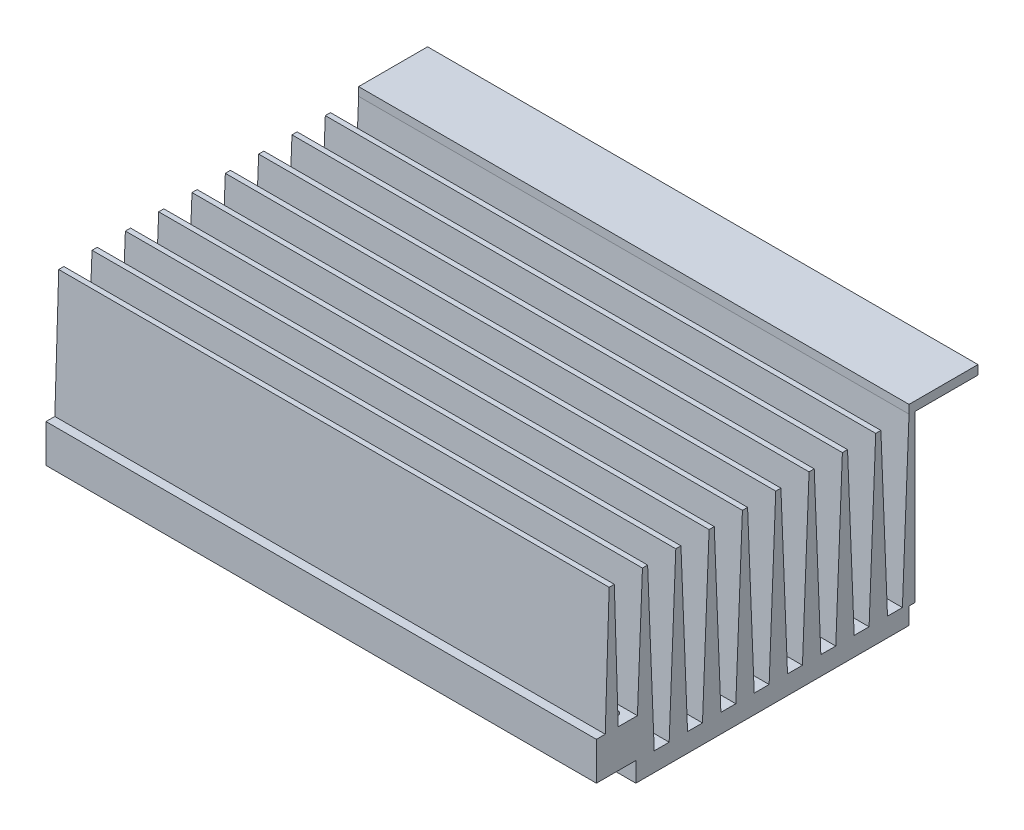
SolidWorks part; units mm, degrees
ref_plane "Front Plane" through (0, 0, 0) normal (0, 0, 1) x (1, 0, 0)
ref_plane "Top Plane" through (0, 0, 0) normal (0, 1, 0) x (1, 0, 0)
ref_plane "Right Plane" through (0, 0, 0) normal (1, 0, 0) x (0, 0, -1)
sketch "Sketch1" plane through (0, 0, 0) normal (0, 1, 0) x (1, 0, 0)
  line L1 (0, 0) -> (195.4375, 0)
  line L2 (0, 0) -> (0, 97)
  line L3 (0, 97) -> (195.4375, 97)
  line L4 (195.4375, 0) -> (195.4375, 97)
  dimension "D1" = 97
  dimension "D2" = 195.4375
extrude "Boss-Extrude1" add sketch "Sketch1" along normal blind 65
sketch "Sketch2" plane through (0, 0, 0) normal (-1, 0, 0) x (0, 0, 1)
  line L0 (-97, 65) -> (-94.65, 6.7)
  line L2 (-94.65, 6.7) -> (-89.35, 6.7)
  line L3 (-89.35, 6.7) -> (-87, 65)
  line L4 (-97, 65) -> (0, 65) construction
  line L5 (-87, 65) -> (-97, 65)
  line L7 (-97, 0) -> (0, 0) construction
  line L8 (-92, 6.7) -> (-92, 65) construction
  line L37 (-75.1687, 65) -> (-85.1687, 65)
  line L38 (-85.1687, 65) -> (-82.8187, 6.7)
  line L39 (-82.8187, 6.7) -> (-77.5187, 6.7)
  line L40 (-77.5187, 6.7) -> (-75.1687, 65)
  line L41 (-63.3375, 65) -> (-73.3375, 65)
  line L42 (-73.3375, 65) -> (-70.9875, 6.7)
  line L43 (-70.9875, 6.7) -> (-65.6875, 6.7)
  line L44 (-65.6875, 6.7) -> (-63.3375, 65)
  line L45 (-51.5062, 65) -> (-61.5062, 65)
  line L46 (-61.5062, 65) -> (-59.1562, 6.7)
  line L47 (-59.1562, 6.7) -> (-53.8563, 6.7)
  line L48 (-53.8563, 6.7) -> (-51.5062, 65)
  line L49 (-39.675, 65) -> (-49.675, 65)
  line L50 (-49.675, 65) -> (-47.325, 6.7)
  line L51 (-47.325, 6.7) -> (-42.025, 6.7)
  line L52 (-42.025, 6.7) -> (-39.675, 65)
  line L53 (-27.8437, 65) -> (-37.8437, 65)
  line L54 (-37.8437, 65) -> (-35.4937, 6.7)
  line L55 (-35.4937, 6.7) -> (-30.1937, 6.7)
  line L56 (-30.1937, 6.7) -> (-27.8437, 65)
  line L57 (-16.0125, 65) -> (-26.0125, 65)
  line L58 (-26.0125, 65) -> (-23.6625, 6.7)
  line L59 (-23.6625, 6.7) -> (-18.3625, 6.7)
  line L60 (-18.3625, 6.7) -> (-16.0125, 65)
  line L61 (-4.1812, 65) -> (-14.1812, 65)
  line L62 (-14.1812, 65) -> (-11.8313, 6.7)
  line L63 (-11.8313, 6.7) -> (-6.5313, 6.7)
  line L64 (-6.5313, 6.7) -> (-4.1812, 65)
  line L65 (7.65, 65) -> (-2.35, 65)
  line L66 (-2.35, 65) -> (0, 6.7)
  line L67 (0, 6.7) -> (5.3, 6.7)
  line L68 (5.3, 6.7) -> (7.65, 65)
  line L69 (0, 65) -> (0, 0) construction
  point P13 (-7.482, 65)
  point P45 (-1.8807, 65)
  point P46 (0, 6.7)
  dimension "D1" = 10
  dimension "D2" = 5.3
  dimension "D3" = 6.7
  dimension "D4" = 9
extrude "Cut-Extrude1" cut sketch "Sketch2" against normal through all
ref_plane "Plane1" through (0, 7, 0) normal (0, -1, 0) x (-1, 0, 0)
sketch "Sketch4" plane through (0, 7, 0) normal (0, -1, 0) x (-1, 0, 0)
  line L0 (-195.4375, 0) -> (-195.4375, 97) construction
  line L1 (0, 1) -> (-195.4375, 1)
  line L2 (0, 1) -> (0, -14)
  line L3 (0, -14) -> (-195.4375, -14)
  line L4 (-195.4375, 1) -> (-195.4375, -14)
  line L5 (0, 97) -> (0, 0) construction
  point P5 (-148.1218, -9.5046)
  point P6 (-147.4038, 1.3296)
  point P7 (-148.5308, 0.9317)
  point P8 (-149.4906, 0.7439)
  point P12 (0, 1)
  point P15 (0, -7.7852)
  dimension "D1" = 1
  dimension "D2" = 15
extrude "Boss-Extrude2" add sketch "Sketch4" against normal blind 13.5
sketch "Sketch5" plane through (0, 0, 0) normal (-1, 0, 0) x (0, 0, 1)
  line L0 (6.2656, 20.5) -> (7.65, 65)
  line L1 (14, 20.5) -> (-0.5563, 20.5) construction
  line L2 (7.65, 65) -> (9.4813, 65)
  line L3 (9.4813, 65) -> (10.8656, 20.5)
  line L4 (-14.1812, 65) -> (-4.1812, 65) construction
  line L5 (-2.35, 65) -> (7.65, 65) construction
  line L6 (-4.1812, 65) -> (-2.35, 65) construction
  line L7 (6.2656, 20.5) -> (10.8656, 20.5)
  line L8 (8.5656, 65) -> (8.5656, 20.5) construction
  line L10 (-21.0125, 6.7) -> (-9.1813, 6.7) construction
  line L11 (-23.6625, 6.7) -> (-18.3625, 6.7) construction
  line L12 (-11.8313, 6.7) -> (-6.5313, 6.7) construction
  dimension "D1" = 4.6
extrude "Boss-Extrude3" add sketch "Sketch5" against normal up to surface (195.4375 mm away) up to face at (195.4375, 31.8475, -42.2705)
ref_plane "Plane2" through (0, 6, 0) normal (0, -1, 0) x (-1, 0, 0)
sketch "Sketch6" plane through (0, 6, 0) normal (0, -1, 0) x (-1, 0, 0)
  line L0 (-195.4375, 0) -> (-195.4375, 97) construction
  line L1 (0, 97) -> (-195.4375, 97)
  line L2 (0, 97) -> (0, 99.19)
  line L3 (0, 99.19) -> (-195.4375, 99.19)
  line L4 (-195.4375, 97) -> (-195.4375, 99.19)
  line L5 (0, 97) -> (0, 0) construction
  line L6 (-195.4375, 97) -> (0, 97) construction
  dimension "D1" = 2.19
extrude "Boss-Extrude4" add sketch "Sketch6" against normal blind 62
sketch "Sketch7" plane through (0, 0, -99.19) normal (0, 0, -1) x (-1, 0, 0)
  line L0 (0, 68) -> (0, 6) construction
  line L1 (-195.4375, 68) -> (0, 68)
  line L2 (-195.4375, 68) -> (-195.4375, 64.76)
  line L3 (-195.4375, 64.76) -> (0, 64.76)
  line L4 (0, 68) -> (0, 64.76)
  point P7 (0, 63.8371)
  dimension "D1" = 3.24
extrude "Boss-Extrude5" add sketch "Sketch7" along normal blind 22.3
sketch "Sketch8" plane through (0, 6.7, 0) normal (0, 1, 0) x (1, 0, 0)
  line L0 (195.4375, -14) -> (0, -14) construction
  line L1 (195.4375, -14) -> (0, -14)
  line L2 (97.7188, -14) -> (97.7188, 115.2245) construction
  line L3 (195.4375, 0.5563) -> (195.4375, -6.2656) construction
  line L4 (195.4375, 0.5563) -> (195.4375, -6.2656)
  line L5 (195.4375, 94.65) -> (195.4375, 89.35) construction
  line L6 (195.4375, 94.65) -> (195.4375, 89.35)
  circle A0 centre (190.4375, 92) radius 1.5
  circle A1 centre (190.4375, -2.8547) radius 1.5
  circle A2 centre (5, 92) radius 1.5
  circle A3 centre (5, -2.8547) radius 1.5
  point P8 (97.7188, -14)
  point P9 (191.2303, -3.2764)
  point P12 (195.4375, -2.8547)
  point P15 (195.4375, 92)
  point P16 (190.4375, 92)
  dimension "D2" = 3
  dimension "D1" = 5
extrude "Cut-Extrude2" cut sketch "Sketch8" against normal through all and the other way through all contours A2 | A0 | A3 | A1
